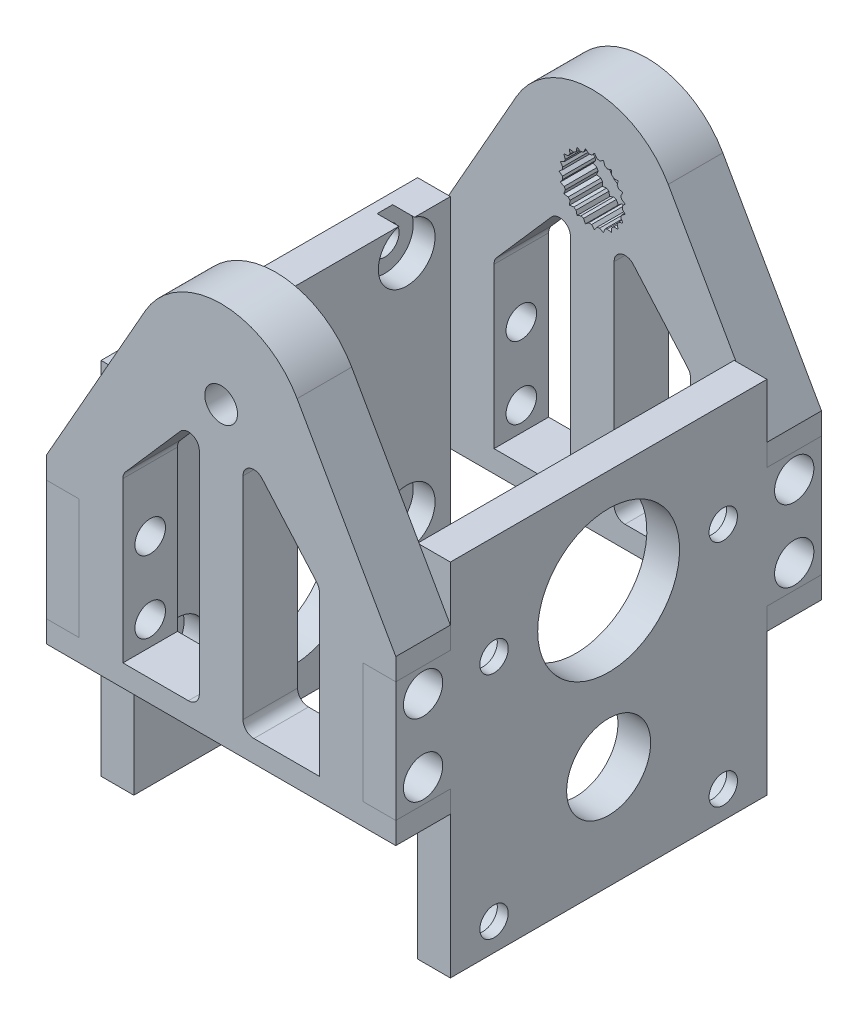
SolidWorks part; units mm, degrees
ref_plane "正面" through (0, 0, 0) normal (0, 0, 1) x (1, 0, 0)
ref_plane "平面" through (0, 0, 0) normal (0, 1, 0) x (1, 0, 0)
ref_plane "右側面" through (0, 0, 0) normal (1, 0, 0) x (0, 0, -1)
sketch "ｽｹｯﾁ1" plane through (0, 0, 0) normal (0, 0, 1) x (1, 0, 0)
  line L0 (-16, -12) -> (-16, -27)
  line L1 (-16, -27) -> (16, -27)
  line L2 (16, -27) -> (16, -12)
  line L3 (16, -12) -> (6.9593, 3.9457)
  line L4 (-6.9593, 3.9457) -> (-16, -12)
  line L5 (0, 0) -> (0, -27) construction
  line L6 (-16, -12) -> (16, -12) construction
  circle A0 centre (0, 0) radius 2.75
  arc A1 (6.9593, 3.9457) -> (-6.9593, 3.9457) centre (0, 0) ccw
  dimension "D1" = 5.5
  dimension "D6" = 8
  dimension "D2" = 16
  dimension "D3" = 16
  dimension "D4" = 12
  dimension "D5" = 15
extrude "ﾎﾞｽ - 押し出し1" add sketch "ｽｹｯﾁ1" along normal blind 3
sketch "ｽｹｯﾁ19" plane through (0, 0, 3) normal (0, 0, 1) x (1, 0, 0)
  line L0 (0, 0) -> (0, 2.75) construction
  line L1 (0, 0) -> (0.3745, 2.7244) construction
  line L2 (0, 0) -> (0.7419, 2.648) construction
  line L3 (0, 0) -> (1.0956, 2.5223) construction
  line L4 (0, 0) -> (1.4289, 2.3497) construction
  line L5 (0, 0) -> (1.7355, 2.1332) construction
  line L6 (0, 0) -> (2.0098, 1.877) construction
  line L7 (0, 0) -> (2.2467, 1.5859) construction
  line L8 (0, 0) -> (2.4417, 1.2652) construction
  line L9 (0, 0) -> (2.5912, 0.9209) construction
  line L10 (0, 0) -> (2.6925, 0.5595) construction
  line L11 (0, 0) -> (2.7436, 0.1877) construction
  line L12 (0, 0) -> (2.7436, -0.1877) construction
  line L13 (0, 0) -> (2.6925, -0.5595) construction
  line L14 (0, 0) -> (2.5912, -0.9209) construction
  line L15 (0, 0) -> (2.4417, -1.2652) construction
  line L16 (0, 0) -> (2.2467, -1.5859) construction
  line L17 (0, 0) -> (2.0098, -1.877) construction
  line L18 (0, 0) -> (1.7355, -2.1332) construction
  line L19 (0, 0) -> (1.4289, -2.3497) construction
  line L20 (0, 0) -> (1.0956, -2.5223) construction
  line L21 (0, 0) -> (0.7419, -2.648) construction
  line L22 (0, 0) -> (0.3745, -2.7244) construction
  line L23 (0, 0) -> (0, -2.75) construction
  line L24 (0, 0) -> (-0.3745, -2.7244) construction
  line L25 (0, 0) -> (-0.7419, -2.648) construction
  line L26 (0, 0) -> (-1.0956, -2.5223) construction
  line L27 (0, 0) -> (-1.4289, -2.3497) construction
  line L28 (0, 0) -> (-1.7355, -2.1332) construction
  line L29 (0, 0) -> (-2.0098, -1.877) construction
  line L30 (0, 0) -> (-2.2467, -1.5859) construction
  line L31 (0, 0) -> (-2.4417, -1.2652) construction
  line L32 (0, 0) -> (-2.5912, -0.9209) construction
  line L33 (0, 0) -> (-2.6925, -0.5595) construction
  line L34 (0, 0) -> (-2.7436, -0.1877) construction
  line L35 (0, 0) -> (-2.7436, 0.1877) construction
  line L36 (0, 0) -> (-2.6925, 0.5595) construction
  line L37 (0, 0) -> (-2.5912, 0.9209) construction
  line L38 (0, 0) -> (-2.4417, 1.2652) construction
  line L39 (0, 0) -> (-2.2467, 1.5859) construction
  line L40 (0, 0) -> (-2.0098, 1.877) construction
  line L41 (0, 0) -> (-1.7355, 2.1332) construction
  line L42 (0, 0) -> (-1.4289, 2.3497) construction
  line L43 (0, 0) -> (-1.0956, 2.5223) construction
  line L44 (0, 0) -> (-0.7419, 2.648) construction
  line L45 (0, 0) -> (-0.3745, 2.7244) construction
  line L46 (0, 0) -> (0.2081, 3.0429) construction
  line L47 (0.2081, 3.0429) -> (-0.0626, 2.7493)
  line L48 (0.2081, 3.0429) -> (0.4364, 2.7152)
  line L49 (-0.0626, 2.7493) -> (0, 0) construction
  line L50 (0, 0) -> (0.4364, 2.7152) construction
  line L51 (1.0214, 2.8739) -> (0.6815, 2.6642)
  line L52 (1.0214, 2.8739) -> (1.1527, 2.4967)
  line L53 (1.7589, 2.4918) -> (1.375, 2.3816)
  line L54 (1.7589, 2.4918) -> (1.7836, 2.0931)
  line L55 (2.3659, 1.9248) -> (1.9666, 1.9223)
  line L56 (2.3659, 1.9248) -> (2.2822, 1.5343)
  line L57 (2.7975, 1.2151) -> (2.4123, 1.3204)
  line L58 (2.7975, 1.2151) -> (2.6115, 0.8617)
  line L59 (3.0216, 0.4153) -> (2.679, 0.6206)
  line L60 (3.0216, 0.4153) -> (2.7472, 0.1252)
  line L61 (3.0216, -0.4153) -> (2.7472, -0.1252)
  line L62 (3.0216, -0.4153) -> (2.679, -0.6206)
  line L63 (2.7975, -1.2151) -> (2.6115, -0.8617)
  line L64 (2.7975, -1.2151) -> (2.4123, -1.3204)
  line L65 (2.3659, -1.9248) -> (2.2822, -1.5343)
  line L66 (2.3659, -1.9248) -> (1.9666, -1.9223)
  line L67 (1.7589, -2.4918) -> (1.7836, -2.0931)
  line L68 (1.7589, -2.4918) -> (1.375, -2.3816)
  line L69 (1.0214, -2.8739) -> (1.1527, -2.4967)
  line L70 (1.0214, -2.8739) -> (0.6815, -2.6642)
  line L71 (0.2081, -3.0429) -> (0.4364, -2.7152)
  line L72 (0.2081, -3.0429) -> (-0.0626, -2.7493)
  line L73 (-0.6205, -2.9862) -> (-0.3123, -2.7322)
  line L74 (-0.6205, -2.9862) -> (-0.802, -2.6304)
  line L75 (-1.4032, -2.708) -> (-1.0379, -2.5466)
  line L76 (-1.4032, -2.708) -> (-1.482, -2.3165)
  line L77 (-2.0818, -2.229) -> (-1.6865, -2.1722)
  line L78 (-2.0818, -2.229) -> (-2.052, -1.8308)
  line L79 (-2.606, -1.5847) -> (-2.21, -1.6366)
  line L80 (-2.606, -1.5847) -> (-2.4699, -1.2093)
  line L81 (-2.9369, -0.8229) -> (-2.5696, -0.9797)
  line L82 (-2.9369, -0.8229) -> (-2.7045, -0.4981)
  line L83 (-3.05, 0) -> (-2.7386, -0.2501)
  line L84 (-3.05, 0) -> (-2.7386, 0.2501)
  line L85 (-2.9369, 0.8229) -> (-2.7045, 0.4981)
  line L86 (-2.9369, 0.8229) -> (-2.5696, 0.9797)
  line L87 (-2.606, 1.5847) -> (-2.4699, 1.2093)
  line L88 (-2.606, 1.5847) -> (-2.21, 1.6366)
  line L89 (-2.0818, 2.229) -> (-2.052, 1.8308)
  line L90 (-2.0818, 2.229) -> (-1.6865, 2.1722)
  line L91 (-1.4032, 2.708) -> (-1.482, 2.3165)
  line L92 (-1.4032, 2.708) -> (-1.0379, 2.5466)
  line L93 (-0.6205, 2.9862) -> (-0.802, 2.6304)
  line L94 (-0.6205, 2.9862) -> (-0.3123, 2.7322)
  circle A0 centre (0, 0) radius 2.75 construction
  arc A1 (0, 2.75) -> (0.3745, 2.7244) centre (0, 0) cw construction
  circle A2 centre (0, 0) radius 3.05 construction
  arc A3 (-0.0626, 2.7493) -> (0.4364, 2.7152) centre (0, 0) cw
  arc A4 (0.6815, 2.6642) -> (1.1527, 2.4967) centre (0, 0) cw
  arc A5 (1.375, 2.3816) -> (1.7836, 2.0931) centre (0, 0) cw
  arc A6 (1.9666, 1.9223) -> (2.2822, 1.5343) centre (0, 0) cw
  arc A7 (2.4123, 1.3204) -> (2.6115, 0.8617) centre (0, 0) cw
  arc A8 (2.679, 0.6206) -> (2.7472, 0.1252) centre (0, 0) cw
  arc A9 (2.7472, -0.1252) -> (2.679, -0.6206) centre (0, 0) cw
  arc A10 (2.6115, -0.8617) -> (2.4123, -1.3204) centre (0, 0) cw
  arc A11 (2.2822, -1.5343) -> (1.9666, -1.9223) centre (0, 0) cw
  arc A12 (1.7836, -2.0931) -> (1.375, -2.3816) centre (0, 0) cw
  arc A13 (1.1527, -2.4967) -> (0.6815, -2.6642) centre (0, 0) cw
  arc A14 (0.4364, -2.7152) -> (-0.0626, -2.7493) centre (0, 0) cw
  arc A15 (-0.3123, -2.7322) -> (-0.802, -2.6304) centre (0, 0) cw
  arc A16 (-1.0379, -2.5466) -> (-1.482, -2.3165) centre (0, 0) cw
  arc A17 (-1.6865, -2.1722) -> (-2.052, -1.8308) centre (0, 0) cw
  arc A18 (-2.21, -1.6366) -> (-2.4699, -1.2093) centre (0, 0) cw
  arc A19 (-2.5696, -0.9797) -> (-2.7045, -0.4981) centre (0, 0) cw
  arc A20 (-2.7386, -0.2501) -> (-2.7386, 0.2501) centre (0, 0) cw
  arc A21 (-2.7045, 0.4981) -> (-2.5696, 0.9797) centre (0, 0) cw
  arc A22 (-2.4699, 1.2093) -> (-2.21, 1.6366) centre (0, 0) cw
  arc A23 (-2.052, 1.8308) -> (-1.6865, 2.1722) centre (0, 0) cw
  arc A24 (-1.482, 2.3165) -> (-1.0379, 2.5466) centre (0, 0) cw
  arc A25 (-0.802, 2.6304) -> (-0.3123, 2.7322) centre (0, 0) cw
  point P7 (0.1877, 2.7436)
  point P52 (0, 0)
  point P60 (0.1877, 2.7436)
  point P126 (0, 0)
  dimension "D2" = 6.1
  dimension "D3" = 10.435
  dimension "D1" = 46
  dimension "D4" = 23
extrude "ｶｯﾄ - 押し出し6" cut sketch "ｽｹｯﾁ19" against normal through all
sketch "ｽｹｯﾁ2" plane through (0, 0, 0) normal (0, 0, -1) x (-1, 0, 0)
  line L5 (16, -12) -> (6.9593, 3.9457)
  line L6 (-6.9593, 3.9457) -> (-16, -12)
  line L7 (-16, -12) -> (-16, -27)
  line L8 (-16, -27) -> (16, -27)
  line L9 (16, -27) -> (16, -12)
  line L10 (16, -12) -> (6.9593, 3.9457)
  line L11 (-6.9593, 3.9457) -> (-16, -12)
  line L12 (-16, -12) -> (-16, -27)
  line L13 (-16, -27) -> (16, -27)
  line L14 (16, -27) -> (16, -12)
  arc A1 (6.9593, 3.9457) -> (-6.9593, 3.9457) centre (0, 0) ccw
  arc A2 (6.9593, 3.9457) -> (-6.9593, 3.9457) centre (0, 0) ccw
  dimension "D1" = 0
extrude "ﾎﾞｽ - 押し出し2" add sketch "ｽｹｯﾁ2" along normal blind 2
ref_plane "平面1" through (0, 0, 33.5) normal (0, 0, 1) x (1, 0, 0)
sketch "ｽｹｯﾁ3" plane through (0, 0, 33.5) normal (0, 0, 1) x (1, 0, 0)
  line L5 (-6.9593, 3.9457) -> (-16, -12)
  line L6 (-16, -12) -> (-16, -27)
  line L7 (-16, -27) -> (16, -27)
  line L8 (16, -27) -> (16, -12)
  line L9 (16, -12) -> (6.9593, 3.9457)
  line L10 (-6.9593, 3.9457) -> (-16, -12)
  line L11 (-16, -12) -> (-16, -27)
  line L12 (-16, -27) -> (16, -27)
  line L13 (16, -27) -> (16, -12)
  line L14 (16, -12) -> (6.9593, 3.9457)
  circle A0 centre (0, 0) radius 2.75 construction
  arc A1 (6.9593, 3.9457) -> (-6.9593, 3.9457) centre (0, 0) ccw
  arc A2 (6.9593, 3.9457) -> (-6.9593, 3.9457) centre (0, 0) ccw
  circle A3 centre (0, 0) radius 2.75 construction
  circle A4 centre (0, 0) radius 3.6
  dimension "D2" = 7.2
  dimension "D1" = 0
extrude "ﾎﾞｽ - 押し出し3" add sketch "ｽｹｯﾁ3" against normal blind 1.5 separate body
sketch "ｽｹｯﾁ4" plane through (0, 0, 33.5) normal (0, 0, 1) x (1, 0, 0)
  line L5 (-6.9593, 3.9457) -> (-16, -12)
  line L6 (-16, -12) -> (-16, -27)
  line L7 (-16, -27) -> (16, -27)
  line L8 (16, -27) -> (16, -12)
  line L9 (16, -12) -> (6.9593, 3.9457)
  line L10 (-6.9593, 3.9457) -> (-16, -12)
  line L11 (-16, -12) -> (-16, -27)
  line L12 (-16, -27) -> (16, -27)
  line L13 (16, -27) -> (16, -12)
  line L14 (16, -12) -> (6.9593, 3.9457)
  arc A1 (6.9593, 3.9457) -> (-6.9593, 3.9457) centre (0, 0) ccw
  arc A2 (6.9593, 3.9457) -> (-6.9593, 3.9457) centre (0, 0) ccw
  dimension "D1" = 0
extrude "ﾎﾞｽ - 押し出し4" add sketch "ｽｹｯﾁ4" along normal blind 3.5
sketch "ｽｹｯﾁ5" plane through (0, 0, -2) normal (0, 0, -1) x (-1, 0, 0)
  line L0 (-16, -12) -> (-16, -27) construction
  line L1 (-16, -14) -> (-13, -14)
  line L2 (-16, -14) -> (-16, -25)
  line L3 (-16, -25) -> (-13, -25)
  line L4 (-13, -14) -> (-13, -25)
  line L5 (-16, -14) -> (-13, -25) construction
  line L6 (-16, -25) -> (-13, -14) construction
  line L7 (16, -27) -> (16, -12) construction
  line L8 (16, -14) -> (13, -14)
  line L9 (16, -14) -> (16, -25)
  line L10 (16, -25) -> (13, -25)
  line L11 (13, -14) -> (13, -25)
  line L12 (16, -14) -> (13, -25) construction
  line L13 (16, -25) -> (13, -14) construction
  line L14 (-16, -27) -> (16, -27) construction
  line L15 (-16, -12) -> (16, -12) construction
  line L16 (-6.9593, 3.9457) -> (-16, -12) construction
  point P4 (-14.5, -19.5)
  point P11 (14.5, -19.5)
  dimension "D1" = 3
  dimension "D2" = 3
  dimension "D3" = 2
  dimension "D4" = 2
extrude "ｶｯﾄ - 押し出し1" cut sketch "ｽｹｯﾁ5" against normal through all
sketch "ｽｹｯﾁ6" plane through (13, 0, 0) normal (1, 0, 0) x (0, 0, -1)
  line L0 (2, -14) -> (-3, -14)
  line L1 (-3, -14) -> (-3, -7)
  line L2 (-3, -7) -> (-32, -7)
  line L3 (-32, -12) -> (-32, 3.9457) construction
  line L4 (-32, -7) -> (-32, -14)
  line L5 (-32, -14) -> (-37, -14)
  line L6 (-37, -14) -> (-37, -25)
  line L7 (-37, -25) -> (-32, -25)
  line L8 (-32, -25) -> (-32, -40)
  line L9 (-32, -40) -> (-3, -40)
  line L10 (-3, -40) -> (-3, -25)
  line L11 (-3, -25) -> (2, -25)
  line L12 (2, -25) -> (2, -14)
  line L13 (-17.5, -7) -> (-17.5, -40) construction
  line L14 (0, 0) -> (-33.5, 0) construction
  line L15 (-7, -37.5) -> (-28, -37.5) construction
  line L16 (-7, -37.5) -> (-7, -16.5) construction
  line L17 (-7, -16.5) -> (-28, -16.5) construction
  line L18 (-28, -37.5) -> (-28, -16.5) construction
  line L19 (-7, -37.5) -> (-28, -16.5) construction
  line L20 (-7, -16.5) -> (-28, -37.5) construction
  line L21 (-33.5, 3.3394) -> (-33.5, -3.3394) construction
  line L22 (2, -23.5) -> (-37, -23.5) construction
  circle A0 centre (-17.5, -16.5) radius 6.5
  circle A1 centre (-28, -16.5) radius 1.3
  circle A2 centre (-7, -16.5) radius 1.3
  circle A3 centre (-28, -37.5) radius 1.3
  circle A4 centre (-7, -37.5) radius 1.3
  circle A5 centre (-17.5, -30.5) radius 6.5 construction
  circle A6 centre (-17.5, -30.5) radius 3.85
  point P24 (-17.5, -27)
  point P43 (-17.5, -23.5)
  dimension "D6" = 2.6
  dimension "D8" = 13
  dimension "D10" = 7.7
  dimension "D1" = 21
  dimension "D2" = 21
  dimension "D3" = 14.5
  dimension "D4" = 13
  dimension "D5" = 21
  dimension "D7" = 20
  dimension "D9" = 27
extrude "ﾎﾞｽ - 押し出し5" add sketch "ｽｹｯﾁ6" along normal up to surface (3 mm away) separate body up to face at (16, -13, 0.5)
sketch "ｽｹｯﾁ8" plane through (-13, 0, 0) normal (-1, 0, 0) x (0, 0, 1)
  line L0 (3, -7) -> (3, -40) construction
  line L1 (32, -7) -> (32, -40) construction
  line L2 (3, -23.5) -> (32, -23.5) construction
  line L12 (-2, -14) -> (-2, -25)
  line L13 (-2, -25) -> (3, -25)
  line L14 (3, -25) -> (3, -40)
  line L15 (3, -40) -> (32, -40)
  line L16 (32, -40) -> (32, -25)
  line L17 (32, -25) -> (37, -25)
  line L18 (37, -25) -> (37, -14)
  line L19 (37, -14) -> (32, -14)
  line L20 (32, -14) -> (32, -7)
  line L21 (32, -7) -> (3, -7)
  line L22 (3, -7) -> (3, -14)
  line L23 (3, -14) -> (-2, -14)
  line L24 (-2, -14) -> (-2, -25)
  line L25 (-2, -25) -> (3, -25)
  line L26 (3, -25) -> (3, -40)
  line L27 (3, -40) -> (32, -40)
  line L28 (32, -40) -> (32, -25)
  line L29 (32, -25) -> (37, -25)
  line L30 (37, -25) -> (37, -14)
  line L31 (37, -14) -> (32, -14)
  line L32 (32, -14) -> (32, -7)
  line L33 (32, -7) -> (3, -7)
  line L34 (3, -7) -> (3, -14)
  line L35 (3, -14) -> (-2, -14)
  circle A0 centre (28, -37.5) radius 1.3 construction
  circle A1 centre (28, -16.5) radius 1.3 construction
  circle A2 centre (7, -37.5) radius 1.3 construction
  circle A3 centre (17.5, -16.5) radius 6.5 construction
  circle A4 centre (7, -16.5) radius 1.3 construction
  circle A5 centre (28, -37.5) radius 1.3 construction
  circle A6 centre (28, -16.5) radius 1.3 construction
  circle A7 centre (7, -37.5) radius 1.3 construction
  circle A8 centre (17.5, -16.5) radius 6.5 construction
  circle A9 centre (7, -16.5) radius 1.3 construction
  circle A10 centre (28, -9.5) radius 1.3
  circle A11 centre (7, -9.5) radius 1.3
  circle A12 centre (28, -30.5) radius 1.3
  circle A13 centre (17.5, -30.5) radius 6.5
  circle A14 centre (7, -30.5) radius 1.3
  circle A15 centre (17.5, -16.5) radius 3.85
  dimension "D2" = 7.7
  dimension "D1" = 0
extrude "ﾎﾞｽ - 押し出し6" add sketch "ｽｹｯﾁ8" along normal up to surface (3 mm away) separate body up to face at (-16, -26, 0.5)
sketch "ｽｹｯﾁ7" plane through (0, 0, -2) normal (0, 0, -1) x (-1, 0, 0)
  line L0 (0, 0) -> (0, -13.5) construction
  line L1 (-16, -27) -> (16, -27) construction
  line L2 (9, -25) -> (-9, -25) construction
  line L3 (9, -25) -> (9, -2) construction
  line L4 (9, -2) -> (-9, -2) construction
  line L5 (-9, -25) -> (-9, -2) construction
  line L6 (9, -25) -> (-9, -2) construction
  line L7 (9, -2) -> (-9, -25) construction
  line L8 (-13, -25) -> (-13, -14) construction
  line L9 (-9, -25) -> (-3, -25)
  line L10 (-2, -24) -> (-2, -4.6614)
  line L11 (-3.7526, -4.0029) -> (-8.7526, -9.7172)
  line L12 (-9, -10.3757) -> (-9, -25)
  line L15 (-16, -14) -> (-13, -14) construction
  line L16 (9, -25) -> (3, -25)
  line L17 (9, -10.3757) -> (9, -25)
  line L18 (3.7526, -4.0029) -> (8.7526, -9.7172)
  line L19 (2, -24) -> (2, -4.6614)
  circle A0 centre (0, 0) radius 1.5
  arc A2 (3, -25) -> (2, -24) centre (3, -24) cw
  arc A3 (-3, -25) -> (-2, -24) centre (-3, -24) ccw
  arc A5 (-2, -4.6614) -> (-3.7526, -4.0029) centre (-3, -4.6614) ccw
  arc A6 (3.7526, -4.0029) -> (2, -4.6614) centre (3, -4.6614) ccw
  arc A7 (9, -10.3757) -> (8.7526, -9.7172) centre (8, -10.3757) ccw
  arc A8 (-8.7526, -9.7172) -> (-9, -10.3757) centre (-8, -10.3757) ccw
  point P28 (2, -25)
  point P31 (-2, -25)
  point P37 (-2, -2)
  point P40 (2, -2)
  point P43 (9, -10)
  point P46 (-9, -10)
  dimension "D1" = 3
  dimension "D8" = 1
  dimension "D2" = 2
  dimension "D3" = 4
  dimension "D4" = 23
  dimension "D5" = 4
  dimension "D6" = 7
extrude "ｶｯﾄ - 押し出し2" cut sketch "ｽｹｯﾁ7" against normal through all
sketch "ｽｹｯﾁ10" plane through (16, 0, 0) normal (1, 0, 0) x (0, 0, -1)
  line L4 (-34.5, -12) -> (-34.5, -27) construction
  line L5 (-32, -12) -> (-37, -12) construction
  line L6 (-32, -27) -> (-37, -27) construction
  line L8 (-0.5, -12) -> (-0.5, -27) construction
  line L9 (-3, -12) -> (2, -12) construction
  line L10 (-3, -27) -> (2, -27) construction
  line L11 (-37, -14) -> (-32, -14) construction
  line L14 (-32, -25) -> (-37, -25) construction
  line L15 (-3, -14) -> (2, -14) construction
  line L16 (2, -25) -> (-3, -25) construction
  point P26 (-34.5, -16.2)
  point P28 (-34.5, -22.8)
  point P30 (-0.5, -16.2)
  point P32 (-0.5, -22.8)
  dimension "D1" = 2.2
  dimension "D2" = 2.2
  dimension "D3" = 2.2
  dimension "D4" = 2.2
hole_wizard "Ø2.8 (2.8) 直径の穴1" positions "ｽｹｯﾁ10" profile "ｽｹｯﾁ11" hole size "Ø2.8" standard "JIS"
sketch "ｽｹｯﾁ11" plane through (16, -22.8, 0.5) normal (0, 1, 0) x (0, 0, -1)
  line L0 (0, 0) -> (0, 14)
  line L1 (0, 14) -> (1.4, 13.1588)
  line L2 (1.4, 13.1588) -> (1.4, 0)
  line L5 (1.4, 0) -> (0, 0)
  line L10 (0, 14) -> (-1.4, 13.1588) construction
  line L11 (0, -6.35) -> (0, 107.95) construction
  dimension "穴の直径" = 2.8
  dimension "穴の深さ" = 14
  dimension "ﾄﾞﾘﾙ角度" = 118
hole_wizard "Ø2.8 (2.8) 直径の穴2" positions "ｽｹｯﾁ12" profile "ｽｹｯﾁ13" hole size "Ø2.8" standard "JIS"
sketch "ｽｹｯﾁ12" plane through (-16, 0, 0) normal (-1, 0, 0) x (0, 0, 1)
  point P0 (34.5, -16.2)
  point P3 (34.5, -22.8)
  point P6 (0.5, -16.2)
  point P9 (0.5, -22.8)
sketch "ｽｹｯﾁ13" plane through (-16, -16.2, 34.5) normal (0, 1, 0) x (0, 0, 1)
  line L0 (0, 0) -> (0, 14)
  line L1 (0, 14) -> (1.4, 13.1588)
  line L2 (1.4, 13.1588) -> (1.4, 0)
  line L5 (1.4, 0) -> (0, 0)
  line L10 (0, 14) -> (-1.4, 13.1588) construction
  line L11 (0, -6.35) -> (0, 107.95) construction
  dimension "穴の直径" = 2.8
  dimension "穴の深さ" = 14
  dimension "ﾄﾞﾘﾙ角度" = 118
hole_wizard "Ø3.6 (3.6) 直径の穴1" positions "ｽｹｯﾁ14" profile "ｽｹｯﾁ16" hole size "Ø3.6" standard "JIS" end condition through all
sketch "ｽｹｯﾁ14" plane through (16, 0, 0) normal (1, 0, 0) x (0, 0, -1)
  point P0 (-34.5, -16.2)
  point P3 (-34.5, -22.8)
  point P6 (-0.5, -16.2)
  point P9 (-0.5, -22.8)
sketch "ｽｹｯﾁ16" plane through (16, -16.2, 34.5) normal (0, 1, 0) x (0, 0, -1)
  line L0 (0, 0) -> (0, 32)
  line L1 (0, 32) -> (1.8, 32)
  line L2 (1.8, 32) -> (1.8, 0)
  line L5 (1.8, 0) -> (0, 0)
  line L11 (0, -6.35) -> (0, 107.95) construction
  dimension "通し穴の直径" = 3.6
  dimension "通し穴の深さ" = 32
sketch "ｽｹｯﾁ17" plane through (13, 0, 0) normal (-1, 0, 0) x (0, 0, 1)
  circle A0 centre (28, -37.5) radius 1.3 construction
  circle A1 centre (7, -37.5) radius 1.3 construction
  circle A2 centre (28, -16.5) radius 1.3 construction
  circle A3 centre (7, -16.5) radius 1.3 construction
  circle A4 centre (28, -37.5) radius 1.3 construction
  circle A5 centre (7, -37.5) radius 1.3 construction
  circle A6 centre (28, -16.5) radius 1.3 construction
  circle A7 centre (7, -16.5) radius 1.3 construction
  circle A8 centre (7, -16.5) radius 2.6
  circle A9 centre (7, -37.5) radius 2.6
  circle A10 centre (28, -37.5) radius 2.6
  circle A11 centre (28, -16.5) radius 2.6
  dimension "D1" = 5.2
extrude "ｶｯﾄ - 押し出し4" cut sketch "ｽｹｯﾁ17" against normal blind 2
sketch "ｽｹｯﾁ18" plane through (-13, 0, 0) normal (1, 0, 0) x (0, 0, -1)
  circle A0 centre (-28, -30.5) radius 1.3 construction
  circle A1 centre (-28, -9.5) radius 1.3 construction
  circle A2 centre (-7, -9.5) radius 1.3 construction
  circle A3 centre (-28, -30.5) radius 1.3 construction
  circle A4 centre (-28, -9.5) radius 1.3 construction
  circle A5 centre (-7, -9.5) radius 1.3 construction
  circle A6 centre (-7, -30.5) radius 1.3 construction
  circle A7 centre (-7, -30.5) radius 1.3 construction
  circle A8 centre (-28, -9.5) radius 2.6
  circle A9 centre (-28, -30.5) radius 2.6
  circle A10 centre (-7, -30.5) radius 2.6
  circle A11 centre (-7, -9.5) radius 2.6
  dimension "D1" = 5.2
extrude "ｶｯﾄ - 押し出し5" cut sketch "ｽｹｯﾁ18" against normal blind 2
equation "\"D2@ｽｹｯﾁ5\"=\"D1@ｽｹｯﾁ5\""
equation "\"D8@ｽｹｯﾁ6\"=12.5+0.5"
equation "\"D1@ｽｹｯﾁ10\"=\"D2@ｽｹｯﾁ10\""
equation "\"D3@ｽｹｯﾁ10\"=\"D2@ｽｹｯﾁ10\""
equation "\"D4@ｽｹｯﾁ10\"=\"D2@ｽｹｯﾁ10\""
equation "\"D3@ｽｹｯﾁ19\"=360/23*2/3"
